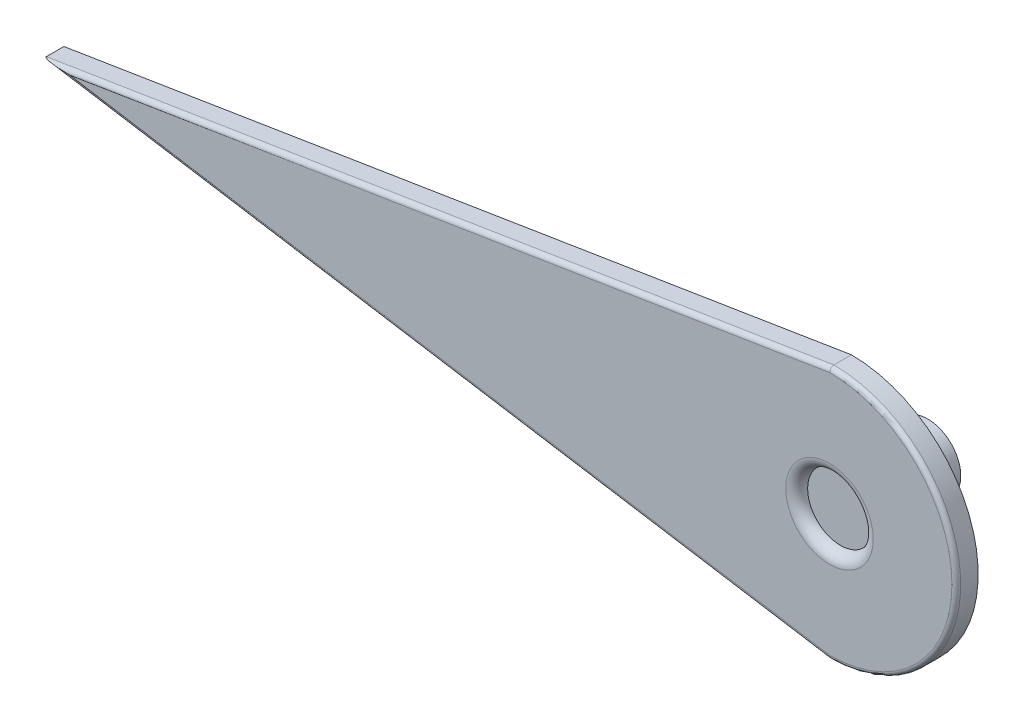
SolidWorks part; units mm, degrees
ref_plane "Front" through (0, 0, 0) normal (0, 0, 1) x (1, 0, 0)
ref_plane "Top" through (0, 0, 0) normal (0, 1, 0) x (1, 0, 0)
ref_plane "Right" through (0, 0, 0) normal (1, 0, 0) x (0, 0, -1)
sketch "Эскиз1" plane through (0, 0, 0) normal (0, 0, 1) x (1, 0, 0)
  line L0 (0, 0) -> (3.6, 0) construction
  line L1 (0, 0) -> (3.6, 0.5796)
  line L2 (0, 0) -> (3.6, -0.5796)
  circle A0 centre (3.6, 0) radius 0.15
  arc A1 (3.6, 0.5796) -> (3.6, -0.5796) centre (3.6, 0) cw
  dimension "D2" = 0.3
  dimension "D1" = 3.6
extrude "Бобышка-Вытянуть1" add sketch "Эскиз1" along normal blind 0.1
sketch "Эскиз2" plane through (0, 0, 0) normal (0, 0, -1) x (-1, 0, 0)
  circle A0 centre (-3.6, 0) radius 0.15 construction
  circle A1 centre (-3.6, 0) radius 0.15
extrude "Бобышка-Вытянуть2" add sketch "Эскиз2" along normal blind 0.35 and the other way blind 0.05 separate body
fillet "Скругление1" radius 0.05 1 edges at (3.75, 0, 0.1)
fillet "Скругление2" radius 0.02 3 edges at (4.1796, 0, 0.1) (1.8, 0.2898, 0.1) (1.8, -0.2898, 0.1)
